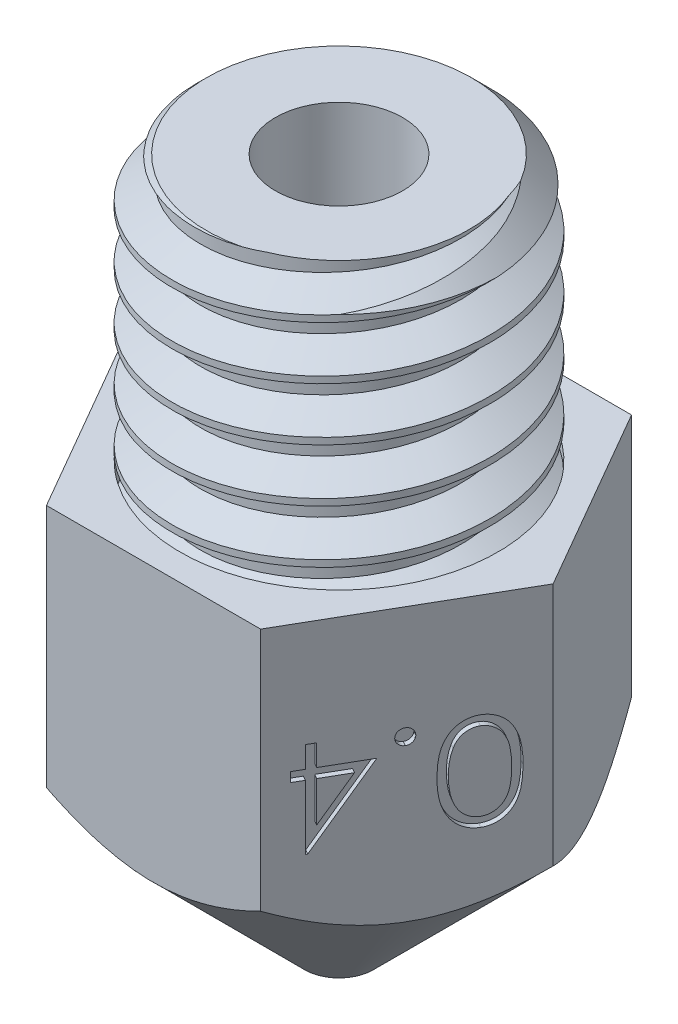
SolidWorks part; units mm, degrees
ref_plane "Alzado" through (0, 0, 0) normal (0, 0, 1) x (1, 0, 0)
ref_plane "Planta" through (0, 0, 0) normal (0, 1, 0) x (1, 0, 0)
ref_plane "Vista lateral" through (0, 0, 0) normal (1, 0, 0) x (0, 0, -1)
sketch "Croquis1" plane through (0, 0, 0) normal (1, 0, 0) x (0, 0, -1)
  line L0 (-1.2, 13) -> (-1.2, 2.2321)
  line L1 (-4.04, 3.39) -> (-0.65, 0)
  line L2 (-4.04, 3.39) -> (-4.04, 8)
  line L3 (-4.04, 8) -> (-3, 8)
  line L4 (-3, 8) -> (-3, 12.5)
  line L5 (-3, 12.5) -> (-2.5, 13)
  line L6 (-2.5, 13) -> (-1.2, 13)
  line L7 (-0.2, 0) -> (-0.2, 0.5)
  line L8 (-1.2, 2.2321) -> (-0.2, 0.5)
  line L9 (-0.65, 0) -> (-0.2, 0)
  line L10 (0, 0) -> (0, 13) construction
  dimension "D1" = 0.2
  dimension "D2" = 0.5
  dimension "D3" = 8
  dimension "D4" = 13
  dimension "D5" = 3
  dimension "D6" = 1.2
  dimension "D7" = 4.04
  dimension "D8" = 0.65
  dimension "D9" = 45
  dimension "D10" = 0.5
  dimension "D11" = 60
  dimension "D12" = 45
revolve "Revolución1" add sketch "Croquis1" angle 360 about L10
sketch "Croquis2" plane through (0, 8, 0) normal (0, 1, 0) x (1, 0, 0)
  line L1 (2.02, 3.4987) -> (-2.02, 3.4987)
  line L2 (-2.02, 3.4987) -> (-4.04, 0)
  line L3 (-4.04, 0) -> (-2.02, -3.4987)
  line L4 (-2.02, -3.4987) -> (2.02, -3.4987)
  line L5 (2.02, -3.4987) -> (4.04, 0)
  line L6 (4.04, 0) -> (2.02, 3.4987)
  circle A0 centre (0, 0) radius 3.4987 construction
  circle A1 centre (0, 0) radius 4.04 construction
  point P1 (-2.02, 3.4987)
extrude "Cortar-Extruir-Lámina1" cut sketch "Croquis2" against normal blind 10 thin thin type one direction wall 10
thread "Rosca1" pitch 1 method cut profile "Perfil de rosca1" start angle 0, offset 1, length 0, pitch 1, diameter 6
ref_plane "Plano1" through (-3, 14, 0) normal (0, 0, 1) x (-1, 0, 0)
sketch "Perfil de rosca1" plane through (-3, 14, 0) normal (0, 0, 1) x (-1, 0, 0)
  line L0 (0, 0) -> (0, 1) construction
  line L11 (0, 0) -> (0, 0.875)
  line L12 (0, 0.875) -> (-0.5413, 0.5625)
  line L13 (-0.5413, 0.5625) -> (-0.5413, 0.3125)
  line L15 (-0.5413, 0.3125) -> (0, 0)
  line L17 (-0.5413, 0.4375) -> (0, 0.4375) construction
  point P2 (0, 0)
  dimension "Pitch" = 1
  dimension "Profile_Angle" = 60
  dimension "Profile_Land" = 0.25
  dimension "Profile_Height" = 0.5413
sketch "Croquis5" plane through (3.03, 0, 1.7494) normal (0.866, 0, 0.5) x (0.5, 0, -0.866)
  line L0 (2.02, 6) -> (-2.02, 6) construction
  line L1 (2.02, 3.39) -> (2.02, 8) construction
  line L2 (-2.02, 3.39) -> (-2.02, 8) construction
  line L3 (-2.02, 8) -> (2.02, 8) construction
  text T0 "0.4" font "Century Gothic" height 1.75
  dimension "D1" = 2
extrude "Cortar-Extruir1" cut sketch "Croquis5" against normal blind 0.1
